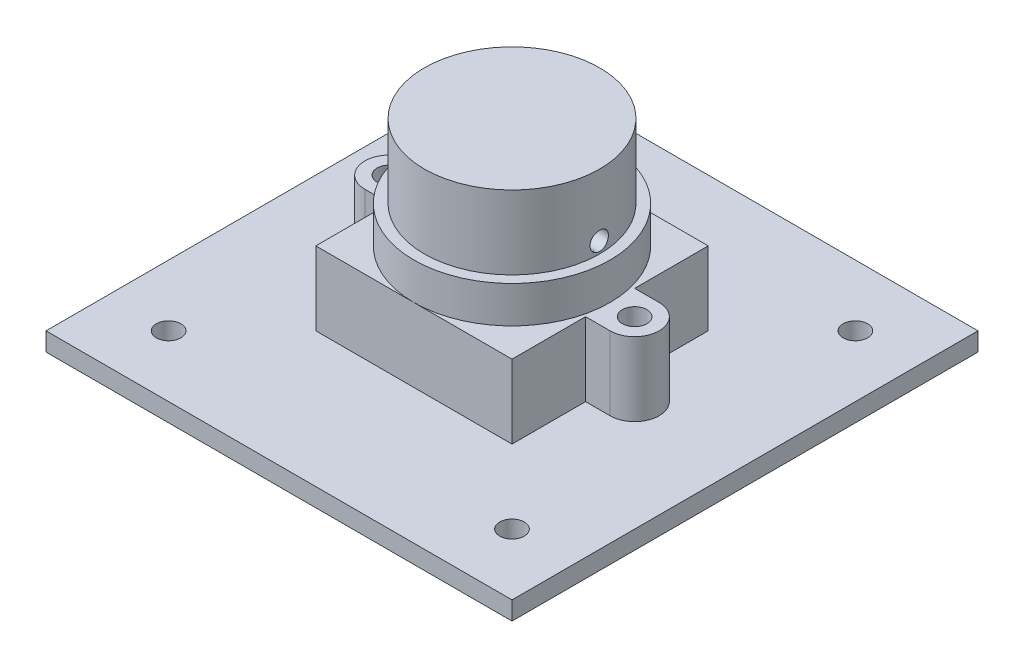
SolidWorks part; units mm, degrees
ref_plane "Front Plane" through (0, 0, 0) normal (0, 0, 1) x (1, 0, 0)
ref_plane "Top Plane" through (0, 0, 0) normal (0, 1, 0) x (1, 0, 0)
ref_plane "Right Plane" through (0, 0, 0) normal (1, 0, 0) x (0, 0, -1)
sketch "Sketch1" plane through (0, 0, 0) normal (0, 1, 0) x (1, 0, 0)
  line L1 (-19, 19) -> (19, 19)
  line L2 (-19, 19) -> (-19, -19)
  line L3 (-19, -19) -> (19, -19)
  line L4 (19, 19) -> (19, -19)
  line L5 (-19, 19) -> (19, -19) construction
  line L6 (-19, -19) -> (19, 19) construction
  point P0 (0, 0)
  dimension "D1" = 38
  dimension "D2" = 38
extrude "Boss-Extrude1" add sketch "Sketch1" along normal blind 1.5
sketch "Sketch2" plane through (0, 1.5, 0) normal (0, 1, 0) x (1, 0, 0)
  line L0 (-10, 2) -> (-8, 2)
  line L1 (-8, 8) -> (8, 8)
  line L2 (-8, 8) -> (-8, 2)
  line L3 (-8, -8) -> (8, -8)
  line L4 (8, 8) -> (8, 2)
  line L5 (-8, 8) -> (8, -8) construction
  line L6 (-8, -8) -> (8, 8) construction
  line L7 (-10, -2) -> (-8, -2)
  line L8 (0, 13.3529) -> (0, -6.3804) construction
  line L9 (10, 2) -> (8, 2)
  line L10 (10, -2) -> (8, -2)
  line L13 (-8, -2) -> (-8, -8)
  line L14 (8, -2) -> (8, -8)
  circle A0 centre (-10, 0) radius 1
  arc A1 (-10, 2) -> (-10, -2) centre (-10, 0) ccw
  circle A2 centre (-10, 0) radius 2 construction
  arc A3 (10, 2) -> (10, -2) centre (10, 0) cw
  circle A4 centre (10, 0) radius 1
  point P0 (0, 0)
  dimension "D3" = 2
  dimension "D1" = 16
  dimension "D2" = 16
  dimension "D5" = 2
  dimension "D4" = 1
extrude "Boss-Extrude2" add sketch "Sketch2" along normal blind 6
sketch "Sketch3" plane through (0, 7.5, 0) normal (0, 1, 0) x (1, 0, 0)
  circle A0 centre (0, 0) radius 8
  dimension "D1" = 16
extrude "Boss-Extrude3" add sketch "Sketch3" along normal blind 3
sketch "Sketch4" plane through (0, 1.5, 0) normal (0, 1, 0) x (1, 0, 0)
  line L0 (19, -19) -> (19, 19) construction
  line L1 (19, 19) -> (-19, 19) construction
  line L2 (-4.0665, 0) -> (5.2171, 0) construction
  line L3 (0, 6.2501) -> (0, -4.7741) construction
  circle A0 centre (14, 14) radius 1
  circle A1 centre (-14, 14) radius 1
  circle A2 centre (14, -14) radius 1
  circle A3 centre (-14, -14) radius 1
  dimension "D1" = 2
  dimension "D2" = 5
  dimension "D3" = 5
extrude "Cut-Extrude1" cut sketch "Sketch4" against normal blind 9
sketch "Sketch5" plane through (0, 10.5, 0) normal (0, 1, 0) x (1, 0, 0)
  circle A0 centre (0, 0) radius 7.15
  dimension "D1" = 14.3
extrude "Boss-Extrude4" add sketch "Sketch5" along normal blind 6
sketch "Sketch6" plane through (0, 0, 0) normal (1, 0, 0) x (0, 0, -1)
  circle A0 centre (0, 11.4329) radius 0.75
  dimension "D1" = 1.5
extrude "Cut-Extrude2" cut sketch "Sketch6" against normal blind 2 from surface starting at face at (0, 16.5, 7.15)
